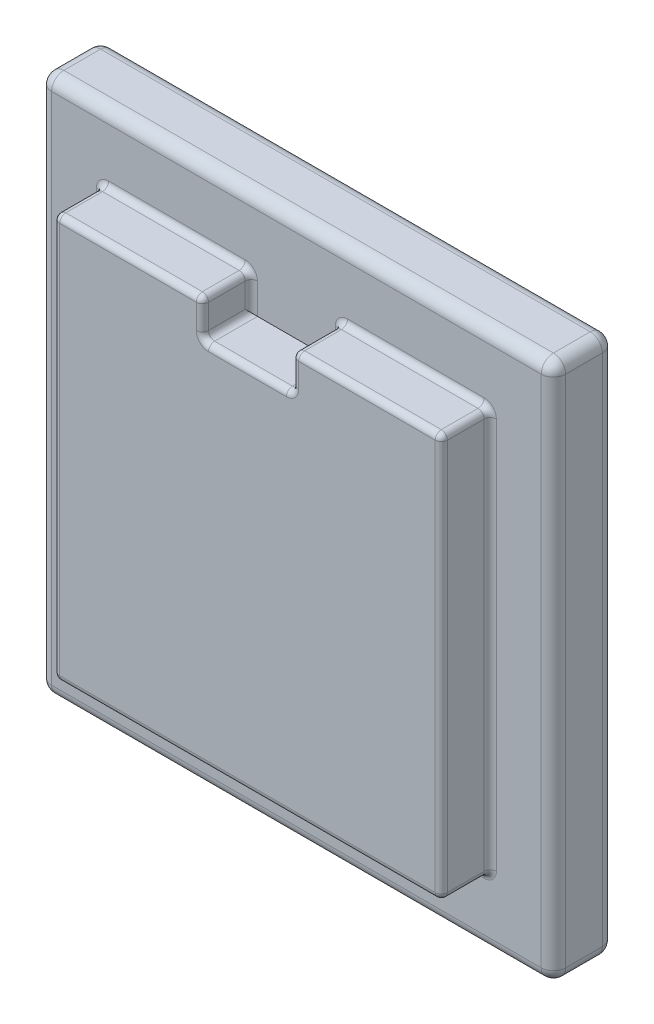
SolidWorks part; units mm, degrees
ref_plane "Front Plane" through (0, 0, 0) normal (0, 0, 1) x (1, 0, 0)
ref_plane "Top Plane" through (0, 0, 0) normal (0, 1, 0) x (1, 0, 0)
ref_plane "Right Plane" through (0, 0, 0) normal (1, 0, 0) x (0, 0, -1)
sketch "Sketch1" plane through (0, 0, 0) normal (0, 0, 1) x (1, 0, 0)
  line L0 (-25.146, 26.1937) -> (-15.494, 26.1937)
  line L1 (-25.146, -26.1937) -> (25.146, -26.1937)
  line L2 (-25.146, -26.1937) -> (-25.146, 26.1937)
  line L3 (-25.146, 26.1937) -> (25.146, 26.1937) construction
  line L4 (25.146, -26.1937) -> (25.146, 26.1937)
  line L5 (-25.146, -26.1937) -> (25.146, 26.1937) construction
  line L6 (-25.146, 26.1937) -> (25.146, -26.1937) construction
  line L7 (-15.494, 26.1937) -> (15.494, 26.1937) construction
  line L11 (15.494, 26.1937) -> (25.146, 26.1937)
  line L12 (-15.494, 26.1937) -> (-5.842, 26.1937)
  line L13 (-5.842, 26.1937) -> (-5.842, 21.4313)
  line L14 (-5.842, 21.4313) -> (5.842, 21.4313)
  line L15 (5.842, 21.4313) -> (5.842, 26.1937)
  line L16 (5.842, 26.1937) -> (15.494, 26.1937)
  line L17 (0, 0) -> (0, 21.4313) construction
  point P0 (0, 0)
  dimension "D1" = 52.3875
  dimension "D2" = 50.292
  dimension "D3" = 47.625
  dimension "D4" = 11.684
extrude "Boss-Extrude1" add sketch "Sketch1" along normal blind 6.35
sketch "Sketch2" plane through (0, 0, 0) normal (0, 0, 1) x (1, 0, 0)
  line L1 (33.3375, -34.925) -> (-33.3375, -34.925)
  line L2 (33.3375, -34.925) -> (33.3375, 34.925)
  line L3 (33.3375, 34.925) -> (-33.3375, 34.925)
  line L4 (-33.3375, -34.925) -> (-33.3375, 34.925)
  line L5 (33.3375, -34.925) -> (-33.3375, 34.925) construction
  line L6 (33.3375, 34.925) -> (-33.3375, -34.925) construction
  point P0 (0, 0)
  dimension "D1" = 66.675
  dimension "D2" = 69.85
extrude "Boss-Extrude2" add sketch "Sketch2" against normal blind 3.175
sketch "Sketch3" plane through (0, 0, -3.175) normal (0, 0, -1) x (-1, 0, 0)
  line L0 (5.715, 27.305) -> (24.892, 27.305)
  line L1 (-24.892, -27.305) -> (24.892, -27.305)
  line L2 (-24.892, -27.305) -> (-24.892, 27.305)
  line L3 (-24.892, 27.305) -> (-5.715, 27.305)
  line L12 (24.892, -27.305) -> (24.892, 27.305)
  line L13 (-24.892, -27.305) -> (24.892, 27.305) construction
  line L14 (-24.892, 27.305) -> (24.892, -27.305) construction
  line L16 (-5.715, 27.305) -> (-5.715, 22.733)
  line L17 (-5.715, 22.733) -> (5.715, 22.733)
  line L18 (5.715, 27.305) -> (5.715, 22.733)
  line L19 (33.3375, -34.925) -> (33.3375, 34.925)
  line L20 (33.3375, 34.925) -> (-33.3375, 34.925)
  line L21 (-33.3375, 34.925) -> (-33.3375, -34.925)
  line L22 (-33.3375, -34.925) -> (33.3375, -34.925)
  line L23 (33.3375, -34.925) -> (33.3375, 34.925)
  line L24 (33.3375, 34.925) -> (-33.3375, 34.925)
  line L25 (-33.3375, 34.925) -> (-33.3375, -34.925)
  line L26 (-33.3375, -34.925) -> (33.3375, -34.925)
  point P2 (0, 0)
  point P14 (0, 22.733)
  point P15 (-8.7339, 21.4956)
  dimension "D2" = 54.61
  dimension "D3" = 49.784
  dimension "D4" = 11.43
  dimension "D5" = 50.038
  dimension "D1" = 0
extrude "Boss-Extrude3" add sketch "Sketch3" along normal blind 4.7625
fillet "Fillet1" radius 1.5875 12 edges at (33.3375, 34.925, -3.9688) (33.3375, -34.925, -3.9688) (-33.3375, -34.925, -3.9688) (-33.3375, 34.925, -3.9688) (33.3375, 0, 0) (0, 34.925, 0) (0, -34.925, 0) (-33.3375, 0, 0) (33.3375, 0, -7.9375) (0, 34.925, -7.9375) (0, -34.925, -7.9375) (-33.3375, 0, -7.9375)
fillet "Fillet2" radius 0.7937 47 edges at (5.842, 26.1937, 3.175) (25.146, 26.1937, 3.175) (25.146, 0, 6.35) (0, -26.1937, 6.35) (-25.146, 0, 6.35) (-15.494, 26.1937, 6.35) (-5.842, 23.8125, 6.35) (0, 21.4313, 6.35) (5.842, 23.8125, 6.35) (15.494, 26.1937, 6.35) (-5.842, 26.1937, 3.175) (-5.842, 21.4313, 3.175) (5.842, 21.4313, 3.175) (25.146, -26.1937, 3.175) (-25.146, 26.1937, 3.175) (-25.146, -26.1937, 3.175) (-5.842, 23.8125, 0) (-15.494, 26.1937, 0) (-25.146, 0, 0) (0, -26.1937, 0) (25.146, 0, 0) (5.842, 23.8125, 0) (15.494, 26.1937, 0) (-5.715, 25.019, -7.9375) (15.3035, 27.305, -7.9375) (24.892, 0, -7.9375) (24.892, 27.305, -5.5563) (0, -27.305, -7.9375) (24.892, -27.305, -5.5563) (-24.892, 0, -7.9375) (-24.892, -27.305, -5.5563) (-5.715, 27.305, -5.5563) (-15.3035, 27.305, -7.9375) (-24.892, 27.305, -5.5563) (0, 22.733, -7.9375) (-5.715, 22.733, -5.5563) (5.715, 27.305, -5.5563) (5.715, 25.019, -7.9375) (5.715, 22.733, -5.5563) (24.892, 0, -3.175) (15.3035, 27.305, -3.175) (5.715, 25.019, -3.175) (0, 22.733, -3.175) (-5.715, 25.019, -3.175) (-15.3035, 27.305, -3.175) (-24.892, 0, -3.175) (0, -27.305, -3.175)
